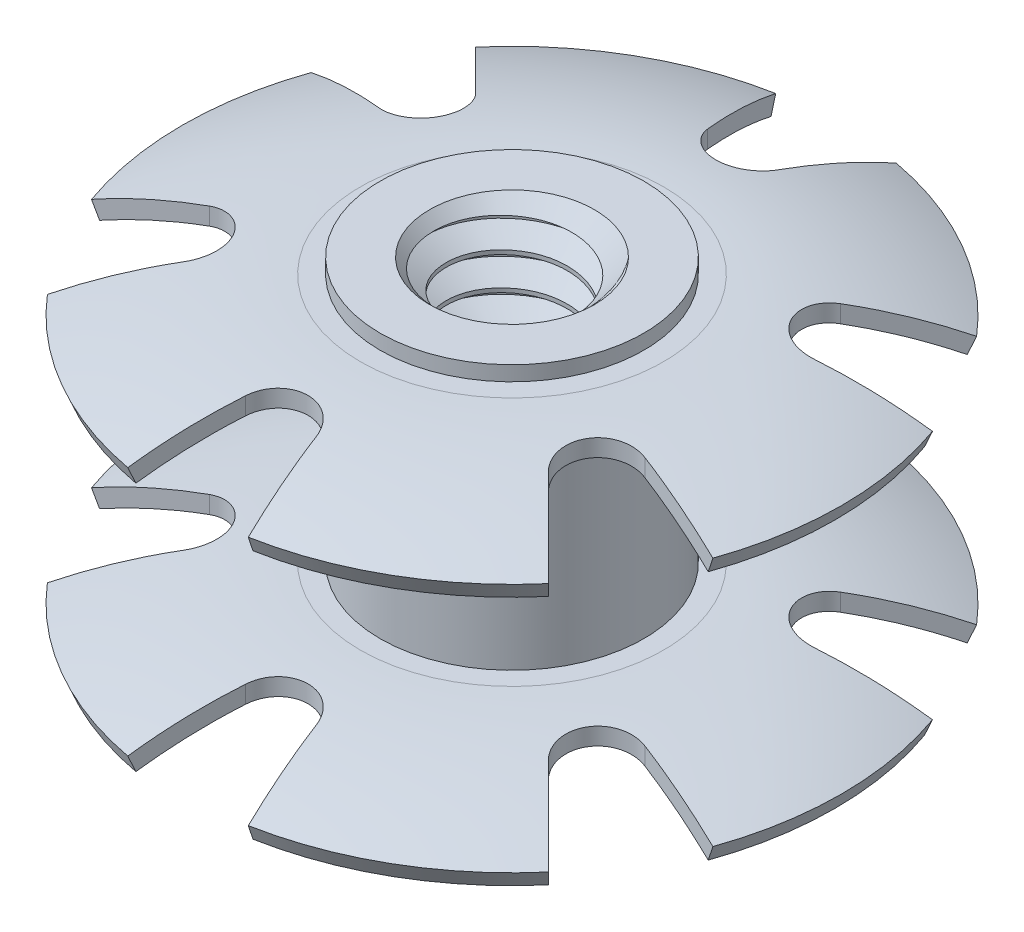
SolidWorks part; units mm, degrees
ref_plane "Front Plane" through (0, 0, 0) normal (0, 0, 1) x (1, 0, 0)
ref_plane "Top Plane" through (0, 0, 0) normal (0, 1, 0) x (1, 0, 0)
ref_plane "Right Plane" through (0, 0, 0) normal (1, 0, 0) x (0, 0, -1)
sketch "Sketch1" plane through (0, 0, 0) normal (0, 0, 1) x (1, 0, 0)
  line L0 (0, 0) -> (0, 5.715) construction
  line L1 (-5.08, 5.715) -> (-3.175, 5.715)
  line L2 (-5.08, 5.715) -> (-5.08, 5.1435)
  line L3 (-5.08, -5.715) -> (-3.175, -5.715)
  line L4 (-3.175, 5.715) -> (-3.175, -5.715)
  line L5 (0, 0) -> (-3.175, 0) construction
  line L6 (-5.08, -5.1435) -> (-5.08, -5.715)
  line L7 (-5.08, 5.1435) -> (-4.572, 5.1435)
  line L9 (-5.08, 4.4831) -> (-4.572, 4.4831)
  line L10 (-4.572, 5.1435) -> (-4.572, 4.4831)
  line L11 (-5.08, -4.4831) -> (-4.572, -4.4831)
  line L12 (-5.08, 4.4831) -> (-5.08, -4.4831)
  line L13 (-5.08, -5.1435) -> (-4.572, -5.1435)
  line L14 (-4.572, -4.4831) -> (-4.572, -5.1435)
  dimension "ID" = 6.35
  dimension "D1" = 10.16
  dimension "D2" = 11.43
  dimension "D3" = 0.6604
  dimension "D4" = 10.287
  dimension "D5" = 9.144
revolve "Revolve1" add sketch "Sketch1" angle 360 about L0
sketch "Sketch2" plane through (0, 5.715, 0) normal (0, 1, 0) x (1, 0, 0)
  circle A0 centre (0, 0) radius 3.175 construction
  circle A1 centre (0, 0) radius 3.175
curve "Helix/Spiral1" pitch 1.27 height 14.605 turns 11.5 parameters "pitch"=1.27
sketch "Sketch3" plane through (0, 0, 0) normal (0, 0, 1) x (1, 0, 0)
  line L0 (2.3501, 6.35) -> (2.3501, 6.1913)
  line L1 (2.3501, 6.1913) -> (3.175, 5.715)
  line L2 (3.175, 5.715) -> (3.175, 6.8263)
  line L3 (2.3501, 6.35) -> (3.175, 6.8263)
  line L4 (2.3501, 6.2706) -> (3.175, 6.2706) construction
  line L5 (2.7626, 6.5881) -> (2.7626, 5.9531) construction
  dimension "D1" = 0.1588
  dimension "D2" = 0.635
  dimension "D3" = 60
sweep "Sweep1" add profiles "Sketch3" path "Helix/Spiral1"
sketch "Sketch4" plane through (0, 5.715, 0) normal (0, 1, 0) x (1, 0, 0)
  circle A1 centre (0, 0) radius 5.08
  circle A2 centre (0, 0) radius 5.08
  dimension "D1" = 0
extrude "Cut-Extrude1" cut sketch "Sketch4" along normal through all
sketch "Sketch5" plane through (0, -5.715, 0) normal (0, -1, 0) x (1, 0, 0)
  circle A1 centre (0, 0) radius 5.08
  circle A2 centre (0, 0) radius 5.08
  dimension "D1" = 0
extrude "Cut-Extrude2" cut sketch "Sketch5" along normal through all
sketch "Sketch6" plane through (0, -5.715, 0) normal (0, -1, 0) x (1, 0, 0)
  circle A1 centre (0, 0) radius 3.175
  circle A2 centre (0, 0) radius 3.175
  dimension "D1" = 0
extrude "Cut-Extrude3" cut sketch "Sketch6" against normal through all draft 45
sketch "Sketch7" plane through (0, 5.715, 0) normal (0, 1, 0) x (1, 0, 0)
  circle A1 centre (0, 0) radius 3.175
  circle A2 centre (0, 0) radius 3.175
  dimension "D1" = 0
extrude "Cut-Extrude4" cut sketch "Sketch7" against normal through all draft 45
sketch "Sketch8" plane through (0, 0, 0) normal (0, 0, 1) x (1, 0, 0)
  line L0 (-5.08, 4.4831) -> (-4.572, 4.4831) construction
  line L1 (-5.842, 5.1435) -> (-4.572, 5.1435)
  line L2 (-12.446, 3.1623) -> (-12.7, 3.7719)
  line L3 (-5.842, 4.4831) -> (-4.572, 4.4831)
  line L4 (-4.572, 5.1435) -> (-4.572, 4.4831)
  line L5 (0, 0) -> (0, 5.715) construction
  line L6 (-5.842, -4.4831) -> (-4.572, -4.4831)
  line L7 (-12.446, -6.4643) -> (-12.7, -5.8547)
  line L8 (-5.842, -5.1435) -> (-4.572, -5.1435)
  line L9 (-4.572, -4.4831) -> (-4.572, -5.1435)
  arc A0 (-5.842, 4.4831) -> (-12.446, 3.1623) centre (-5.842, -12.6873) ccw
  arc A1 (-5.842, 5.1435) -> (-12.7, 3.7719) centre (-5.842, -12.6873) ccw
  arc A2 (-5.842, -5.1435) -> (-12.446, -6.4643) centre (-5.842, -22.3139) ccw
  arc A3 (-5.842, -4.4831) -> (-12.7, -5.8547) centre (-5.842, -22.3139) ccw
  dimension "D1" = 11.684
  dimension "D2" = 1.9812
revolve "Revolve2" add sketch "Sketch8" angle 360 about L5
sketch "Sketch9" plane through (0, 5.715, 0) normal (0, 1, 0) x (1, 0, 0)
  line L0 (0, 5.842) -> (0, 12.7) construction
  line L1 (-1.363, 8.9058) -> (-2.3223, 12.4859)
  line L2 (1.363, 8.9058) -> (2.3223, 12.4859)
  circle A0 centre (0, 0) radius 5.842 construction
  circle A1 centre (0, 0) radius 12.7 construction
  arc A2 (-1.363, 8.9058) -> (1.363, 8.9058) centre (0, 9.271) ccw
  arc A3 (2.3223, 12.4859) -> (-2.3223, 12.4859) centre (0, 0) ccw
  dimension "D1" = 1.4111
  dimension "D2" = 15
extrude "Cut-Extrude5" cut sketch "Sketch9" against normal through all
pattern_circular "CirPattern1" count 6 over 360 about axis through (0, 0, 0) along (0, 1, 0) of "Cut-Extrude5"
sketch "Sketch10" plane through (0, 5.715, 0) normal (0, 1, 0) x (1, 0, 0)
  circle A0 centre (0, 0) radius 12.7
equation "\"D1@Sketch1\" = \"ID@Sketch1\"*1.6"
equation "\"D2@Sketch1\" = \"ID@Sketch1\"*1.8"
equation "\"D4@Sketch1\" = \"D2@Sketch1\"*.9"
equation "\"D5@Sketch1\" = \"D1@Sketch1\"*.9"
equation "\"D3@Helix/Spiral1\" = \"D2@Sketch1\"+.125"
equation "\"D1@Sketch3\" = \"pitch@Helix/Spiral1\"*.125"
equation "\"D2@Sketch3\" = \"pitch@Helix/Spiral1\"*.5"
equation "\"D1@Sketch8\" = \"D1@Sketch1\"*1.15"
equation "\"D1@Sketch9\" = \"OD@Sketch8\"/18"
